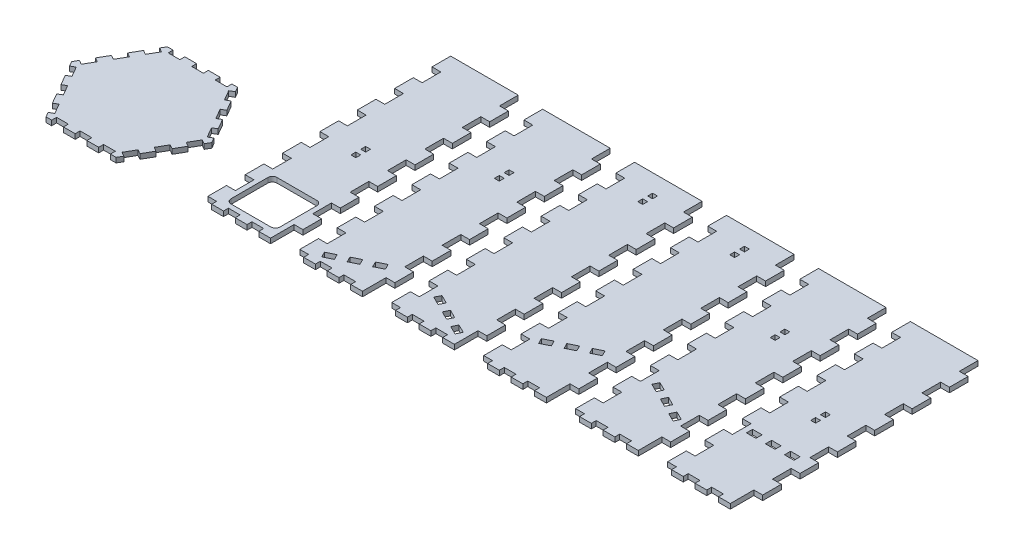
SolidWorks part; units mm, degrees
ref_plane "Front Plane" through (0, 0, 0) normal (0, 0, 1) x (1, 0, 0)
ref_plane "Top Plane" through (0, 0, 0) normal (0, 1, 0) x (1, 0, 0)
ref_plane "Right Plane" through (0, 0, 0) normal (1, 0, 0) x (0, 0, -1)
sketch "Sketch1" plane through (0, 0, 0) normal (0, 1, 0) x (1, 0, 0)
  line L0 (-22.87, -39.612) -> (-19.175, -39.612)
  line L13 (-19.175, -39.612) -> (-19.175, -36.412)
  line L14 (-19.175, -36.412) -> (-11.505, -36.412)
  line L15 (-11.505, -36.412) -> (-11.505, -39.612)
  line L16 (-11.505, -39.612) -> (-3.835, -39.612)
  line L17 (-3.835, -39.612) -> (-3.835, -36.412)
  line L18 (-3.835, -36.412) -> (3.835, -36.412)
  line L19 (3.835, -36.412) -> (3.835, -39.612)
  line L21 (-45.74, 0) -> (-43.8925, -3.2)
  line L22 (3.835, -39.612) -> (11.505, -39.612)
  line L23 (11.505, -39.612) -> (11.505, -36.412)
  line L24 (11.505, -36.412) -> (19.175, -36.412)
  line L25 (19.175, -36.412) -> (19.175, -39.612)
  line L26 (19.175, -39.612) -> (22.87, -39.612)
  line L27 (22.87, -39.612) -> (24.7175, -36.412)
  line L28 (45.74, 0) -> (22.87, 39.612) construction
  line L29 (24.7175, -36.412) -> (21.9462, -34.812)
  line L30 (21.9462, -34.812) -> (25.7812, -28.1696)
  line L31 (25.7812, -28.1696) -> (28.5525, -29.7696)
  line L32 (28.5525, -29.7696) -> (32.3875, -23.1272)
  line L33 (32.3875, -23.1272) -> (29.6162, -21.5272)
  line L34 (29.6162, -21.5272) -> (33.4512, -14.8848)
  line L35 (33.4512, -14.8848) -> (36.2225, -16.4848)
  line L36 (36.2225, -16.4848) -> (40.0575, -9.8424)
  line L37 (40.0575, -9.8424) -> (37.2862, -8.2424)
  line L38 (37.2862, -8.2424) -> (41.1212, -1.6)
  line L39 (41.1212, -1.6) -> (43.8925, -3.2)
  line L40 (43.8925, -3.2) -> (45.74, 0)
  line L41 (45.74, 0) -> (43.8925, 3.2)
  line L42 (22.87, 39.612) -> (-22.87, 39.612) construction
  line L43 (-22.87, 39.612) -> (-45.74, 0) construction
  line L44 (43.8925, 3.2) -> (41.1212, 1.6)
  line L45 (41.1212, 1.6) -> (37.2862, 8.2424)
  line L46 (37.2862, 8.2424) -> (40.0575, 9.8424)
  line L47 (40.0575, 9.8424) -> (36.2225, 16.4848)
  line L48 (36.2225, 16.4848) -> (33.4512, 14.8848)
  line L49 (33.4512, 14.8848) -> (29.6162, 21.5272)
  line L50 (29.6162, 21.5272) -> (32.3875, 23.1272)
  line L51 (32.3875, 23.1272) -> (28.5525, 29.7696)
  line L52 (28.5525, 29.7696) -> (25.7812, 28.1696)
  line L53 (25.7812, 28.1696) -> (21.9462, 34.812)
  line L54 (21.9462, 34.812) -> (24.7175, 36.412)
  line L55 (24.7175, 36.412) -> (22.87, 39.612)
  line L56 (22.87, 39.612) -> (19.175, 39.612)
  line L57 (-45.74, 0) -> (-22.87, -39.612) construction
  line L58 (-22.87, -39.612) -> (22.87, -39.612) construction
  line L59 (19.175, 39.612) -> (19.175, 36.412)
  line L60 (19.175, 36.412) -> (11.505, 36.412)
  line L61 (11.505, 36.412) -> (11.505, 39.612)
  line L62 (11.505, 39.612) -> (3.835, 39.612)
  line L63 (3.835, 39.612) -> (3.835, 36.412)
  line L64 (3.835, 36.412) -> (-3.835, 36.412)
  line L65 (-3.835, 36.412) -> (-3.835, 39.612)
  line L66 (-3.835, 39.612) -> (-11.505, 39.612)
  line L67 (-11.505, 39.612) -> (-11.505, 36.412)
  line L68 (-11.505, 36.412) -> (-19.175, 36.412)
  line L69 (-19.175, 36.412) -> (-19.175, 39.612)
  line L70 (-19.175, 39.612) -> (-22.87, 39.612)
  line L71 (-22.87, 39.612) -> (-24.7175, 36.412)
  line L72 (22.87, -39.612) -> (45.74, 0) construction
  line L73 (-43.8925, -3.2) -> (-41.1212, -1.6)
  line L74 (-24.7175, 36.412) -> (-21.9462, 34.812)
  line L75 (-21.9462, 34.812) -> (-25.7812, 28.1696)
  line L76 (-25.7812, 28.1696) -> (-28.5525, 29.7696)
  line L77 (-28.5525, 29.7696) -> (-32.3875, 23.1272)
  line L78 (-32.3875, 23.1272) -> (-29.6162, 21.5272)
  line L79 (-29.6162, 21.5272) -> (-33.4512, 14.8848)
  line L80 (-33.4512, 14.8848) -> (-36.2225, 16.4848)
  line L81 (-36.2225, 16.4848) -> (-40.0575, 9.8424)
  line L82 (-40.0575, 9.8424) -> (-37.2862, 8.2424)
  line L83 (-37.2862, 8.2424) -> (-41.1212, 1.6)
  line L84 (-41.1212, 1.6) -> (-43.8925, 3.2)
  line L85 (-43.8925, 3.2) -> (-45.74, 0)
  line L86 (-41.1212, -1.6) -> (-37.2862, -8.2424)
  line L87 (-37.2862, -8.2424) -> (-40.0575, -9.8424)
  line L88 (-40.0575, -9.8424) -> (-36.2225, -16.4848)
  line L89 (-36.2225, -16.4848) -> (-33.4512, -14.8848)
  line L90 (-33.4512, -14.8848) -> (-29.6162, -21.5272)
  line L91 (-29.6162, -21.5272) -> (-32.3875, -23.1272)
  line L92 (-32.3875, -23.1272) -> (-28.5525, -29.7696)
  line L93 (-28.5525, -29.7696) -> (-25.7812, -28.1696)
  line L94 (-25.7812, -28.1696) -> (-21.9462, -34.812)
  line L95 (-21.9462, -34.812) -> (-24.7175, -36.412)
  line L96 (-24.7175, -36.412) -> (-22.87, -39.612)
  line L97 (-21.9462, -34.812) -> (-19.175, -39.612) construction
  line L102 (19.175, -36.412) -> (24.7175, -36.412) construction
  line L103 (-19.175, -36.412) -> (-24.7175, -36.412) construction
  line L104 (80.5528, -34.8794) -> (88.2227, -34.8794)
  line L105 (88.2227, -34.8794) -> (88.2227, -31.6794)
  line L106 (88.2227, -31.6794) -> (95.8927, -31.6794)
  line L107 (95.8927, -31.6794) -> (95.8927, -34.8794)
  line L108 (95.8927, -34.8794) -> (103.5627, -34.8794)
  line L109 (103.5627, -34.8794) -> (103.5627, -31.6794)
  line L110 (103.5627, -31.6794) -> (111.2327, -31.6794)
  line L111 (111.2327, -31.6794) -> (111.2327, -34.8794)
  line L112 (111.2327, -34.8794) -> (118.9027, -34.8794)
  line L113 (80.5528, -34.8794) -> (80.5528, -31.6794)
  line L114 (80.5528, -31.6794) -> (74.8102, -31.6794)
  line L115 (74.8102, -31.6794) -> (74.8102, -19.4911)
  line L116 (74.8102, -19.4911) -> (80.5528, -19.4911)
  line L117 (80.5528, -19.4911) -> (80.5528, -7.3028)
  line L118 (80.5528, -7.3028) -> (74.8102, -7.3028)
  line L121 (118.9027, -7.3028) -> (124.6452, -7.3028)
  line L122 (124.6452, -7.3028) -> (124.6452, -19.4911)
  line L123 (124.6452, -19.4911) -> (118.9027, -19.4911)
  line L124 (118.9027, -19.4911) -> (118.9027, -34.8794)
  line L126 (21.9462, -34.812) -> (19.175, -39.612) construction
  line L250 (140.5528, -34.8794) -> (148.2227, -34.8794)
  line L265 (148.2227, -34.8794) -> (148.2227, -31.6794)
  line L266 (148.2227, -31.6794) -> (155.8927, -31.6794)
  line L267 (155.8927, -31.6794) -> (155.8927, -34.8794)
  line L268 (155.8927, -34.8794) -> (163.5627, -34.8794)
  line L269 (163.5627, -34.8794) -> (163.5627, -31.6794)
  line L270 (74.8102, -7.3028) -> (74.8102, 4.8855)
  line L271 (74.8102, 4.8855) -> (80.5528, 4.8855)
  line L272 (80.5528, 4.8855) -> (80.5528, 17.0739)
  line L273 (80.5528, 17.0739) -> (74.8102, 17.0739)
  line L274 (74.8102, 17.0739) -> (74.8102, 29.2622)
  line L275 (74.8102, 29.2622) -> (80.5528, 29.2622)
  line L276 (80.5528, 29.2622) -> (80.5528, 41.4505)
  line L277 (80.5528, 41.4505) -> (74.8102, 41.4505)
  line L278 (74.8102, 41.4505) -> (74.8102, 53.6388)
  line L279 (74.8102, 53.6388) -> (80.5528, 53.6388)
  line L280 (80.5528, 53.6388) -> (80.5528, 65.8271)
  line L281 (80.5528, 65.8271) -> (74.8102, 65.8271)
  line L282 (74.8102, 65.8271) -> (74.8102, 78.0154)
  line L283 (74.8102, 78.0154) -> (80.5528, 78.0154)
  line L284 (80.5528, 78.0154) -> (80.5528, 90.2037)
  line L285 (80.5528, 90.2037) -> (74.8102, 90.2037)
  line L286 (74.8102, 90.2037) -> (74.8102, 102.392)
  line L287 (74.8102, 102.392) -> (80.5528, 102.392)
  line L288 (80.5528, 102.392) -> (80.5528, 114.5803)
  line L289 (80.5528, 114.5803) -> (74.8102, 114.5803)
  line L290 (74.8102, 114.5803) -> (74.8102, 126.7686)
  line L291 (118.9027, -7.3028) -> (118.9027, 4.8855)
  line L292 (118.9027, 4.8855) -> (124.6452, 4.8855)
  line L293 (124.6452, 4.8855) -> (124.6452, 17.0739)
  line L294 (124.6452, 17.0739) -> (118.9027, 17.0739)
  line L295 (118.9027, 17.0739) -> (118.9027, 29.2622)
  line L296 (118.9027, 29.2622) -> (124.6452, 29.2622)
  line L297 (124.6452, 29.2622) -> (124.6452, 41.4505)
  line L298 (124.6452, 41.4505) -> (118.9027, 41.4505)
  line L299 (118.9027, 41.4505) -> (118.9027, 53.6388)
  line L300 (118.9027, 53.6388) -> (124.6452, 53.6388)
  line L301 (124.6452, 53.6388) -> (124.6452, 65.8271)
  line L302 (124.6452, 65.8271) -> (118.9027, 65.8271)
  line L303 (118.9027, 65.8271) -> (118.9027, 78.0154)
  line L304 (118.9027, 78.0154) -> (124.6452, 78.0154)
  line L305 (124.6452, 78.0154) -> (124.6452, 90.2037)
  line L306 (124.6452, 90.2037) -> (118.9027, 90.2037)
  line L307 (118.9027, 90.2037) -> (118.9027, 102.392)
  line L308 (118.9027, 102.392) -> (124.6452, 102.392)
  line L309 (124.6452, 102.392) -> (124.6452, 114.5803)
  line L310 (124.6452, 114.5803) -> (118.9027, 114.5803)
  line L311 (118.9027, 114.5803) -> (118.9027, 126.7686)
  line L312 (163.5627, -31.6794) -> (171.2327, -31.6794)
  line L313 (171.2327, -31.6794) -> (171.2327, -34.8794)
  line L314 (171.2327, -34.8794) -> (178.9027, -34.8794)
  line L315 (140.5528, -34.8794) -> (140.5528, -31.6794)
  line L316 (140.5528, -31.6794) -> (134.8102, -31.6794)
  line L317 (134.8102, -31.6794) -> (134.8102, -19.4911)
  line L318 (134.8102, -19.4911) -> (140.5528, -19.4911)
  line L319 (140.5528, -19.4911) -> (140.5528, -7.3028)
  line L320 (140.5528, -7.3028) -> (134.8102, -7.3028)
  line L322 (178.9027, -7.3028) -> (184.6452, -7.3028)
  line L323 (184.6452, -7.3028) -> (184.6452, -19.4911)
  line L324 (184.6452, -19.4911) -> (178.9027, -19.4911)
  line L325 (178.9027, -19.4911) -> (178.9027, -34.8794)
  line L326 (134.8102, -7.3028) -> (134.8102, 4.8855)
  line L327 (134.8102, 4.8855) -> (140.5528, 4.8855)
  line L328 (140.5528, 4.8855) -> (140.5528, 17.0739)
  line L329 (140.5528, 17.0739) -> (134.8102, 17.0739)
  line L330 (134.8102, 17.0739) -> (134.8102, 29.2622)
  line L331 (134.8102, 29.2622) -> (140.5528, 29.2622)
  line L332 (140.5528, 29.2622) -> (140.5528, 41.4505)
  line L333 (140.5528, 41.4505) -> (134.8102, 41.4505)
  line L334 (134.8102, 41.4505) -> (134.8102, 53.6388)
  line L335 (134.8102, 53.6388) -> (140.5528, 53.6388)
  line L336 (140.5528, 53.6388) -> (140.5528, 65.8271)
  line L337 (140.5528, 65.8271) -> (134.8102, 65.8271)
  line L338 (134.8102, 65.8271) -> (134.8102, 78.0154)
  line L339 (134.8102, 78.0154) -> (140.5528, 78.0154)
  line L340 (140.5528, 78.0154) -> (140.5528, 90.2037)
  line L341 (140.5528, 90.2037) -> (134.8102, 90.2037)
  line L342 (134.8102, 90.2037) -> (134.8102, 102.392)
  line L343 (134.8102, 102.392) -> (140.5528, 102.392)
  line L344 (140.5528, 102.392) -> (140.5528, 114.5803)
  line L345 (140.5528, 114.5803) -> (134.8102, 114.5803)
  line L346 (134.8102, 114.5803) -> (134.8102, 126.7686)
  line L347 (178.9027, -7.3028) -> (178.9027, 4.8855)
  line L348 (178.9027, 4.8855) -> (184.6452, 4.8855)
  line L349 (184.6452, 4.8855) -> (184.6452, 17.0739)
  line L350 (184.6452, 17.0739) -> (178.9027, 17.0739)
  line L351 (178.9027, 17.0739) -> (178.9027, 29.2622)
  line L352 (178.9027, 29.2622) -> (184.6452, 29.2622)
  line L353 (184.6452, 29.2622) -> (184.6452, 41.4505)
  line L354 (184.6452, 41.4505) -> (178.9027, 41.4505)
  line L355 (178.9027, 41.4505) -> (178.9027, 53.6388)
  line L356 (178.9027, 53.6388) -> (184.6452, 53.6388)
  line L357 (184.6452, 53.6388) -> (184.6452, 65.8271)
  line L358 (184.6452, 65.8271) -> (178.9027, 65.8271)
  line L359 (178.9027, 65.8271) -> (178.9027, 78.0154)
  line L360 (178.9027, 78.0154) -> (184.6452, 78.0154)
  line L361 (184.6452, 78.0154) -> (184.6452, 90.2037)
  line L362 (184.6452, 90.2037) -> (178.9027, 90.2037)
  line L363 (178.9027, 90.2037) -> (178.9027, 102.392)
  line L364 (178.9027, 102.392) -> (184.6452, 102.392)
  line L365 (184.6452, 102.392) -> (184.6452, 114.5803)
  line L366 (184.6452, 114.5803) -> (178.9027, 114.5803)
  line L367 (178.9027, 114.5803) -> (178.9027, 126.7686)
  line L369 (200.5528, -34.8794) -> (208.2227, -34.8794)
  line L370 (208.2227, -34.8794) -> (208.2227, -31.6794)
  line L371 (208.2227, -31.6794) -> (215.8927, -31.6794)
  line L372 (215.8927, -31.6794) -> (215.8927, -34.8794)
  line L373 (215.8927, -34.8794) -> (223.5627, -34.8794)
  line L374 (223.5627, -34.8794) -> (223.5627, -31.6794)
  line L375 (223.5627, -31.6794) -> (231.2327, -31.6794)
  line L376 (231.2327, -31.6794) -> (231.2327, -34.8794)
  line L377 (231.2327, -34.8794) -> (238.9027, -34.8794)
  line L378 (200.5528, -34.8794) -> (200.5528, -31.6794)
  line L379 (200.5528, -31.6794) -> (194.8102, -31.6794)
  line L380 (194.8102, -31.6794) -> (194.8102, -19.4911)
  line L381 (194.8102, -19.4911) -> (200.5528, -19.4911)
  line L382 (200.5528, -19.4911) -> (200.5528, -7.3028)
  line L383 (200.5528, -7.3028) -> (194.8102, -7.3028)
  line L385 (238.9027, -7.3028) -> (244.6452, -7.3028)
  line L386 (244.6452, -7.3028) -> (244.6452, -19.4911)
  line L387 (244.6452, -19.4911) -> (238.9027, -19.4911)
  line L388 (238.9027, -19.4911) -> (238.9027, -34.8794)
  line L389 (194.8102, -7.3028) -> (194.8102, 4.8855)
  line L390 (194.8102, 4.8855) -> (200.5528, 4.8855)
  line L391 (200.5528, 4.8855) -> (200.5528, 17.0739)
  line L392 (200.5528, 17.0739) -> (194.8102, 17.0739)
  line L393 (194.8102, 17.0739) -> (194.8102, 29.2622)
  line L394 (194.8102, 29.2622) -> (200.5528, 29.2622)
  line L395 (200.5528, 29.2622) -> (200.5528, 41.4505)
  line L396 (200.5528, 41.4505) -> (194.8102, 41.4505)
  line L397 (194.8102, 41.4505) -> (194.8102, 53.6388)
  line L398 (194.8102, 53.6388) -> (200.5528, 53.6388)
  line L399 (200.5528, 53.6388) -> (200.5528, 65.8271)
  line L400 (200.5528, 65.8271) -> (194.8102, 65.8271)
  line L401 (194.8102, 65.8271) -> (194.8102, 78.0154)
  line L402 (194.8102, 78.0154) -> (200.5528, 78.0154)
  line L403 (200.5528, 78.0154) -> (200.5528, 90.2037)
  line L404 (200.5528, 90.2037) -> (194.8102, 90.2037)
  line L405 (194.8102, 90.2037) -> (194.8102, 102.392)
  line L406 (194.8102, 102.392) -> (200.5528, 102.392)
  line L407 (200.5528, 102.392) -> (200.5528, 114.5803)
  line L408 (200.5528, 114.5803) -> (194.8102, 114.5803)
  line L409 (194.8102, 114.5803) -> (194.8102, 126.7686)
  line L410 (238.9027, -7.3028) -> (238.9027, 4.8855)
  line L411 (238.9027, 4.8855) -> (244.6452, 4.8855)
  line L412 (244.6452, 4.8855) -> (244.6452, 17.0739)
  line L413 (244.6452, 17.0739) -> (238.9027, 17.0739)
  line L414 (238.9027, 17.0739) -> (238.9027, 29.2622)
  line L415 (238.9027, 29.2622) -> (244.6452, 29.2622)
  line L416 (244.6452, 29.2622) -> (244.6452, 41.4505)
  line L417 (244.6452, 41.4505) -> (238.9027, 41.4505)
  line L418 (238.9027, 41.4505) -> (238.9027, 53.6388)
  line L419 (238.9027, 53.6388) -> (244.6452, 53.6388)
  line L420 (244.6452, 53.6388) -> (244.6452, 65.8271)
  line L421 (244.6452, 65.8271) -> (238.9027, 65.8271)
  line L422 (238.9027, 65.8271) -> (238.9027, 78.0154)
  line L423 (238.9027, 78.0154) -> (244.6452, 78.0154)
  line L424 (244.6452, 78.0154) -> (244.6452, 90.2037)
  line L425 (244.6452, 90.2037) -> (238.9027, 90.2037)
  line L426 (238.9027, 90.2037) -> (238.9027, 102.392)
  line L427 (238.9027, 102.392) -> (244.6452, 102.392)
  line L428 (244.6452, 102.392) -> (244.6452, 114.5803)
  line L429 (244.6452, 114.5803) -> (238.9027, 114.5803)
  line L430 (238.9027, 114.5803) -> (238.9027, 126.7686)
  line L432 (260.5528, -34.8794) -> (268.2227, -34.8794)
  line L433 (268.2227, -34.8794) -> (268.2227, -31.6794)
  line L434 (268.2227, -31.6794) -> (275.8927, -31.6794)
  line L435 (275.8927, -31.6794) -> (275.8927, -34.8794)
  line L436 (275.8927, -34.8794) -> (283.5627, -34.8794)
  line L437 (283.5627, -34.8794) -> (283.5627, -31.6794)
  line L438 (283.5627, -31.6794) -> (291.2327, -31.6794)
  line L439 (291.2327, -31.6794) -> (291.2327, -34.8794)
  line L440 (291.2327, -34.8794) -> (298.9027, -34.8794)
  line L441 (260.5528, -34.8794) -> (260.5528, -31.6794)
  line L442 (260.5528, -31.6794) -> (254.8102, -31.6794)
  line L443 (254.8102, -31.6794) -> (254.8102, -19.4911)
  line L444 (254.8102, -19.4911) -> (260.5528, -19.4911)
  line L445 (260.5528, -19.4911) -> (260.5528, -7.3028)
  line L446 (260.5528, -7.3028) -> (254.8102, -7.3028)
  line L448 (298.9027, -7.3028) -> (304.6452, -7.3028)
  line L449 (304.6452, -7.3028) -> (304.6452, -19.4911)
  line L450 (304.6452, -19.4911) -> (298.9027, -19.4911)
  line L451 (298.9027, -19.4911) -> (298.9027, -34.8794)
  line L452 (254.8102, -7.3028) -> (254.8102, 4.8855)
  line L453 (254.8102, 4.8855) -> (260.5528, 4.8855)
  line L454 (260.5528, 4.8855) -> (260.5528, 17.0739)
  line L455 (260.5528, 17.0739) -> (254.8102, 17.0739)
  line L456 (254.8102, 17.0739) -> (254.8102, 29.2622)
  line L457 (254.8102, 29.2622) -> (260.5528, 29.2622)
  line L458 (260.5528, 29.2622) -> (260.5528, 41.4505)
  line L459 (260.5528, 41.4505) -> (254.8102, 41.4505)
  line L460 (254.8102, 41.4505) -> (254.8102, 53.6388)
  line L461 (254.8102, 53.6388) -> (260.5528, 53.6388)
  line L462 (260.5528, 53.6388) -> (260.5528, 65.8271)
  line L463 (260.5528, 65.8271) -> (254.8102, 65.8271)
  line L464 (254.8102, 65.8271) -> (254.8102, 78.0154)
  line L465 (254.8102, 78.0154) -> (260.5528, 78.0154)
  line L466 (260.5528, 78.0154) -> (260.5528, 90.2037)
  line L467 (260.5528, 90.2037) -> (254.8102, 90.2037)
  line L468 (254.8102, 90.2037) -> (254.8102, 102.392)
  line L469 (254.8102, 102.392) -> (260.5528, 102.392)
  line L470 (260.5528, 102.392) -> (260.5528, 114.5803)
  line L471 (260.5528, 114.5803) -> (254.8102, 114.5803)
  line L472 (254.8102, 114.5803) -> (254.8102, 126.7686)
  line L473 (298.9027, -7.3028) -> (298.9027, 4.8855)
  line L474 (298.9027, 4.8855) -> (304.6452, 4.8855)
  line L475 (304.6452, 4.8855) -> (304.6452, 17.0739)
  line L476 (304.6452, 17.0739) -> (298.9027, 17.0739)
  line L477 (298.9027, 17.0739) -> (298.9027, 29.2622)
  line L478 (298.9027, 29.2622) -> (304.6452, 29.2622)
  line L479 (304.6452, 29.2622) -> (304.6452, 41.4505)
  line L480 (304.6452, 41.4505) -> (298.9027, 41.4505)
  line L481 (298.9027, 41.4505) -> (298.9027, 53.6388)
  line L482 (298.9027, 53.6388) -> (304.6452, 53.6388)
  line L483 (304.6452, 53.6388) -> (304.6452, 65.8271)
  line L484 (304.6452, 65.8271) -> (298.9027, 65.8271)
  line L485 (298.9027, 65.8271) -> (298.9027, 78.0154)
  line L486 (298.9027, 78.0154) -> (304.6452, 78.0154)
  line L487 (304.6452, 78.0154) -> (304.6452, 90.2037)
  line L488 (304.6452, 90.2037) -> (298.9027, 90.2037)
  line L489 (298.9027, 90.2037) -> (298.9027, 102.392)
  line L490 (298.9027, 102.392) -> (304.6452, 102.392)
  line L491 (304.6452, 102.392) -> (304.6452, 114.5803)
  line L492 (304.6452, 114.5803) -> (298.9027, 114.5803)
  line L493 (298.9027, 114.5803) -> (298.9027, 126.7686)
  line L495 (320.5528, -34.8794) -> (328.2227, -34.8794)
  line L496 (328.2227, -34.8794) -> (328.2227, -31.6794)
  line L497 (328.2227, -31.6794) -> (335.8927, -31.6794)
  line L498 (335.8927, -31.6794) -> (335.8927, -34.8794)
  line L499 (335.8927, -34.8794) -> (343.5627, -34.8794)
  line L500 (343.5627, -34.8794) -> (343.5627, -31.6794)
  line L501 (343.5627, -31.6794) -> (351.2327, -31.6794)
  line L502 (351.2327, -31.6794) -> (351.2327, -34.8794)
  line L503 (351.2327, -34.8794) -> (358.9027, -34.8794)
  line L504 (320.5528, -34.8794) -> (320.5528, -31.6794)
  line L505 (320.5528, -31.6794) -> (314.8102, -31.6794)
  line L506 (314.8102, -31.6794) -> (314.8102, -19.4911)
  line L507 (314.8102, -19.4911) -> (320.5528, -19.4911)
  line L508 (320.5528, -19.4911) -> (320.5528, -7.3028)
  line L509 (320.5528, -7.3028) -> (314.8102, -7.3028)
  line L511 (358.9027, -7.3028) -> (364.6452, -7.3028)
  line L512 (364.6452, -7.3028) -> (364.6452, -19.4911)
  line L513 (364.6452, -19.4911) -> (358.9027, -19.4911)
  line L514 (358.9027, -19.4911) -> (358.9027, -34.8794)
  line L515 (314.8102, -7.3028) -> (314.8102, 4.8855)
  line L516 (314.8102, 4.8855) -> (320.5528, 4.8855)
  line L517 (320.5528, 4.8855) -> (320.5528, 17.0739)
  line L518 (320.5528, 17.0739) -> (314.8102, 17.0739)
  line L519 (314.8102, 17.0739) -> (314.8102, 29.2622)
  line L520 (314.8102, 29.2622) -> (320.5528, 29.2622)
  line L521 (320.5528, 29.2622) -> (320.5528, 41.4505)
  line L522 (320.5528, 41.4505) -> (314.8102, 41.4505)
  line L523 (314.8102, 41.4505) -> (314.8102, 53.6388)
  line L524 (314.8102, 53.6388) -> (320.5528, 53.6388)
  line L525 (320.5528, 53.6388) -> (320.5528, 65.8271)
  line L526 (320.5528, 65.8271) -> (314.8102, 65.8271)
  line L527 (314.8102, 65.8271) -> (314.8102, 78.0154)
  line L528 (314.8102, 78.0154) -> (320.5528, 78.0154)
  line L529 (320.5528, 78.0154) -> (320.5528, 90.2037)
  line L530 (320.5528, 90.2037) -> (314.8102, 90.2037)
  line L531 (314.8102, 90.2037) -> (314.8102, 102.392)
  line L532 (314.8102, 102.392) -> (320.5528, 102.392)
  line L533 (320.5528, 102.392) -> (320.5528, 114.5803)
  line L534 (320.5528, 114.5803) -> (314.8102, 114.5803)
  line L535 (314.8102, 114.5803) -> (314.8102, 126.7686)
  line L536 (358.9027, -7.3028) -> (358.9027, 4.8855)
  line L537 (358.9027, 4.8855) -> (364.6452, 4.8855)
  line L538 (364.6452, 4.8855) -> (364.6452, 17.0739)
  line L539 (364.6452, 17.0739) -> (358.9027, 17.0739)
  line L540 (358.9027, 17.0739) -> (358.9027, 29.2622)
  line L541 (358.9027, 29.2622) -> (364.6452, 29.2622)
  line L542 (364.6452, 29.2622) -> (364.6452, 41.4505)
  line L543 (364.6452, 41.4505) -> (358.9027, 41.4505)
  line L544 (358.9027, 41.4505) -> (358.9027, 53.6388)
  line L545 (358.9027, 53.6388) -> (364.6452, 53.6388)
  line L546 (364.6452, 53.6388) -> (364.6452, 65.8271)
  line L547 (364.6452, 65.8271) -> (358.9027, 65.8271)
  line L548 (358.9027, 65.8271) -> (358.9027, 78.0154)
  line L549 (358.9027, 78.0154) -> (364.6452, 78.0154)
  line L550 (364.6452, 78.0154) -> (364.6452, 90.2037)
  line L551 (364.6452, 90.2037) -> (358.9027, 90.2037)
  line L552 (358.9027, 90.2037) -> (358.9027, 102.392)
  line L553 (358.9027, 102.392) -> (364.6452, 102.392)
  line L554 (364.6452, 102.392) -> (364.6452, 114.5803)
  line L555 (364.6452, 114.5803) -> (358.9027, 114.5803)
  line L556 (358.9027, 114.5803) -> (358.9027, 126.7686)
  line L558 (380.5528, -34.8794) -> (388.2227, -34.8794)
  line L559 (388.2227, -34.8794) -> (388.2227, -31.6794)
  line L560 (388.2227, -31.6794) -> (395.8927, -31.6794)
  line L561 (395.8927, -31.6794) -> (395.8927, -34.8794)
  line L562 (395.8927, -34.8794) -> (403.5627, -34.8794)
  line L563 (403.5627, -34.8794) -> (403.5627, -31.6794)
  line L564 (403.5627, -31.6794) -> (411.2327, -31.6794)
  line L565 (411.2327, -31.6794) -> (411.2327, -34.8794)
  line L566 (411.2327, -34.8794) -> (418.9027, -34.8794)
  line L567 (380.5528, -34.8794) -> (380.5528, -31.6794)
  line L568 (380.5528, -31.6794) -> (374.8102, -31.6794)
  line L569 (374.8102, -31.6794) -> (374.8102, -19.4911)
  line L570 (374.8102, -19.4911) -> (380.5528, -19.4911)
  line L571 (380.5528, -19.4911) -> (380.5528, -7.3028)
  line L572 (380.5528, -7.3028) -> (374.8102, -7.3028)
  line L574 (418.9027, -7.3028) -> (424.6452, -7.3028)
  line L575 (424.6452, -7.3028) -> (424.6452, -19.4911)
  line L576 (424.6452, -19.4911) -> (418.9027, -19.4911)
  line L577 (418.9027, -19.4911) -> (418.9027, -34.8794)
  line L578 (374.8102, -7.3028) -> (374.8102, 4.8855)
  line L579 (374.8102, 4.8855) -> (380.5528, 4.8855)
  line L580 (380.5528, 4.8855) -> (380.5528, 17.0739)
  line L581 (380.5528, 17.0739) -> (374.8102, 17.0739)
  line L582 (374.8102, 17.0739) -> (374.8102, 29.2622)
  line L583 (374.8102, 29.2622) -> (380.5528, 29.2622)
  line L584 (380.5528, 29.2622) -> (380.5528, 41.4505)
  line L585 (380.5528, 41.4505) -> (374.8102, 41.4505)
  line L586 (374.8102, 41.4505) -> (374.8102, 53.6388)
  line L587 (374.8102, 53.6388) -> (380.5528, 53.6388)
  line L588 (380.5528, 53.6388) -> (380.5528, 65.8271)
  line L589 (380.5528, 65.8271) -> (374.8102, 65.8271)
  line L590 (374.8102, 65.8271) -> (374.8102, 78.0154)
  line L591 (374.8102, 78.0154) -> (380.5528, 78.0154)
  line L592 (380.5528, 78.0154) -> (380.5528, 90.2037)
  line L593 (380.5528, 90.2037) -> (374.8102, 90.2037)
  line L594 (374.8102, 90.2037) -> (374.8102, 102.392)
  line L595 (374.8102, 102.392) -> (380.5528, 102.392)
  line L596 (380.5528, 102.392) -> (380.5528, 114.5803)
  line L597 (380.5528, 114.5803) -> (374.8102, 114.5803)
  line L598 (374.8102, 114.5803) -> (374.8102, 126.7686)
  line L599 (418.9027, -7.3028) -> (418.9027, 4.8855)
  line L600 (418.9027, 4.8855) -> (424.6452, 4.8855)
  line L601 (424.6452, 4.8855) -> (424.6452, 17.0739)
  line L602 (424.6452, 17.0739) -> (418.9027, 17.0739)
  line L603 (418.9027, 17.0739) -> (418.9027, 29.2622)
  line L604 (418.9027, 29.2622) -> (424.6452, 29.2622)
  line L605 (424.6452, 29.2622) -> (424.6452, 41.4505)
  line L606 (424.6452, 41.4505) -> (418.9027, 41.4505)
  line L607 (418.9027, 41.4505) -> (418.9027, 53.6388)
  line L608 (418.9027, 53.6388) -> (424.6452, 53.6388)
  line L609 (424.6452, 53.6388) -> (424.6452, 65.8271)
  line L610 (424.6452, 65.8271) -> (418.9027, 65.8271)
  line L611 (418.9027, 65.8271) -> (418.9027, 78.0154)
  line L612 (418.9027, 78.0154) -> (424.6452, 78.0154)
  line L613 (424.6452, 78.0154) -> (424.6452, 90.2037)
  line L614 (424.6452, 90.2037) -> (418.9027, 90.2037)
  line L615 (418.9027, 90.2037) -> (418.9027, 102.392)
  line L616 (418.9027, 102.392) -> (424.6452, 102.392)
  line L617 (424.6452, 102.392) -> (424.6452, 114.5803)
  line L618 (424.6452, 114.5803) -> (418.9027, 114.5803)
  line L619 (418.9027, 114.5803) -> (418.9027, 126.7686)
  line L621 (144.4326, -25.24) -> (149.9783, -22.4678)
  line L622 (144.4326, -25.24) -> (146.2212, -28.8179)
  line L623 (146.2212, -28.8179) -> (151.7669, -26.0457)
  line L624 (149.9783, -22.4678) -> (151.7669, -26.0457)
  line L625 (155.524, -19.6956) -> (161.0697, -16.9234)
  line L626 (155.524, -19.6956) -> (157.3126, -23.2735)
  line L627 (157.3126, -23.2735) -> (162.8583, -20.5012)
  line L628 (161.0697, -16.9234) -> (162.8583, -20.5012)
  line L632 (166.6154, -14.1512) -> (172.1611, -11.3789)
  line L633 (166.6154, -14.1512) -> (168.404, -17.729)
  line L634 (168.404, -17.729) -> (173.9497, -14.9568)
  line L635 (172.1611, -11.3789) -> (173.9497, -14.9568)
  line L636 (118.9027, 126.7686) -> (74.8102, 126.7686)
  line L637 (134.8102, 126.7686) -> (178.9027, 126.7686)
  line L638 (194.8102, 126.7686) -> (238.9027, 126.7686)
  line L639 (254.8102, 126.7686) -> (298.9027, 126.7686)
  line L640 (314.8102, 126.7686) -> (358.9027, 126.7686)
  line L641 (374.8102, 126.7686) -> (418.9027, 126.7686)
  line L642 (-41.1212, -1.6) -> (-42.045, 0) construction
  line L643 (-42.045, 0) -> (-41.1212, 1.6) construction
  line L644 (41.1212, -1.6) -> (42.045, 0) construction
  line L645 (42.045, 0) -> (41.1212, 1.6) construction
  line L646 (-21.0225, -36.412) -> (-22.87, -39.612) construction
  line L647 (21.0225, -36.412) -> (22.87, -39.612) construction
  line L648 (138.7077, -31.6794) -> (145.8635, -28.1023) construction
  line L649 (173.592, -14.2412) -> (180.7477, -10.6642) construction
  line L650 (189.7277, 136.633) -> (189.7277, -43.0289) construction
  line L651 (138.7077, -34.8794) -> (180.7477, -34.8794) construction
  line L652 (207.2943, -11.3789) -> (205.5058, -14.9568)
  line L653 (211.0515, -17.729) -> (205.5058, -14.9568)
  line L654 (212.84, -14.1512) -> (211.0515, -17.729)
  line L655 (212.84, -14.1512) -> (207.2943, -11.3789)
  line L656 (218.3857, -16.9234) -> (216.5972, -20.5012)
  line L657 (222.1429, -23.2735) -> (216.5972, -20.5012)
  line L658 (223.9314, -19.6956) -> (222.1429, -23.2735)
  line L659 (223.9314, -19.6956) -> (218.3857, -16.9234)
  line L660 (229.4771, -22.4678) -> (227.6886, -26.0457)
  line L661 (233.2343, -28.8179) -> (227.6886, -26.0457)
  line L662 (235.0228, -25.24) -> (233.2343, -28.8179)
  line L663 (235.0228, -25.24) -> (229.4771, -22.4678)
  line L664 (252.6938, -10.4795) -> (309.7277, -10.4795) construction
  line L665 (258.7077, -34.8794) -> (300.7477, -34.8794) construction
  line L666 (258.7077, -10.4795) -> (265.8635, -6.9025) construction
  line L667 (265.8635, -6.9025) -> (264.0749, -3.3246)
  line L668 (264.0749, -3.3246) -> (269.6206, -0.5524)
  line L669 (269.6206, -0.5524) -> (271.4092, -4.1302)
  line L670 (271.4092, -4.1302) -> (265.8635, -6.9025)
  line L671 (275.1663, 2.2199) -> (276.9549, -1.358)
  line L672 (276.9549, -1.358) -> (282.5006, 1.4142)
  line L673 (282.5006, 1.4142) -> (280.712, 4.9921)
  line L674 (280.712, 4.9921) -> (275.1663, 2.2199)
  line L675 (286.2577, 7.7643) -> (288.0463, 4.1864)
  line L676 (288.0463, 4.1864) -> (293.592, 6.9586)
  line L677 (293.592, 6.9586) -> (291.8034, 10.5365)
  line L678 (291.8034, 10.5365) -> (286.2577, 7.7643)
  line L679 (293.592, 6.9586) -> (300.7477, 10.5357) construction
  line L680 (309.7277, 136.633) -> (309.7277, -43.0289) construction
  line L681 (327.652, 10.5365) -> (333.1977, 7.7643)
  line L682 (325.8635, 6.9586) -> (327.652, 10.5365)
  line L683 (331.4092, 4.1864) -> (325.8635, 6.9586)
  line L684 (333.1977, 7.7643) -> (331.4092, 4.1864)
  line L685 (338.7434, 4.9921) -> (344.2891, 2.2199)
  line L686 (336.9549, 1.4142) -> (338.7434, 4.9921)
  line L687 (342.5006, -1.358) -> (336.9549, 1.4142)
  line L688 (344.2891, 2.2199) -> (342.5006, -1.358)
  line L689 (348.0463, -4.1302) -> (353.592, -6.9025)
  line L690 (349.8348, -0.5524) -> (348.0463, -4.1302)
  line L691 (355.3805, -3.3246) -> (349.8348, -0.5524)
  line L692 (353.592, -6.9025) -> (355.3805, -3.3246)
  line L693 (384.2277, 14.3606) -> (384.2277, 10.3606)
  line L694 (384.2277, 10.3606) -> (390.4277, 10.3606)
  line L695 (390.4277, 10.3606) -> (390.4277, 14.3606)
  line L696 (390.4277, 14.3606) -> (384.2277, 14.3606)
  line L697 (396.6277, 14.3606) -> (396.6277, 10.3606)
  line L698 (396.6277, 10.3606) -> (402.8277, 10.3606)
  line L699 (402.8277, 10.3606) -> (402.8277, 14.3606)
  line L700 (402.8277, 14.3606) -> (396.6277, 14.3606)
  line L701 (409.0277, 14.3606) -> (409.0277, 10.3606)
  line L702 (409.0277, 10.3606) -> (415.2277, 10.3606)
  line L703 (415.2277, 10.3606) -> (415.2277, 14.3606)
  line L704 (415.2277, 14.3606) -> (409.0277, 14.3606)
  line L705 (384.2277, 10.3606) -> (380.5528, 10.3606) construction
  line L706 (415.2277, 10.3606) -> (418.9027, 10.3606) construction
  line L707 (86.7528, 1.5206) -> (112.7027, 1.5206)
  line L708 (112.7027, -28.4794) -> (86.7528, -28.4794)
  line L709 (83.7528, -1.4794) -> (83.7528, -25.4794)
  line L710 (115.7027, -1.4794) -> (115.7027, -25.4794)
  line L711 (249.7277, 136.633) -> (249.7277, -43.0289) construction
  line L712 (398.1277, 47.9606) -> (401.3277, 47.9606)
  line L713 (398.1277, 47.9606) -> (398.1277, 44.7606)
  line L714 (398.1277, 44.7606) -> (401.3277, 44.7606)
  line L715 (401.3277, 47.9606) -> (401.3277, 44.7606)
  line L716 (398.1277, 41.5606) -> (401.3277, 41.5606)
  line L717 (398.1277, 41.5606) -> (398.1277, 38.3606)
  line L718 (398.1277, 38.3606) -> (401.3277, 38.3606)
  line L719 (401.3277, 41.5606) -> (401.3277, 38.3606)
  line L720 (98.1277, 41.5606) -> (98.1277, 38.3606)
  line L721 (101.3277, 38.3606) -> (98.1277, 38.3606)
  line L722 (101.3277, 41.5606) -> (101.3277, 38.3606)
  line L723 (101.3277, 41.5606) -> (98.1277, 41.5606)
  line L724 (98.1277, 47.9606) -> (98.1277, 44.7606)
  line L725 (101.3277, 44.7606) -> (98.1277, 44.7606)
  line L726 (101.3277, 47.9606) -> (101.3277, 44.7606)
  line L727 (101.3277, 47.9606) -> (98.1277, 47.9606)
  line L728 (158.1277, 75.1606) -> (158.1277, 71.9606)
  line L729 (161.3277, 71.9606) -> (158.1277, 71.9606)
  line L730 (161.3277, 75.1606) -> (161.3277, 71.9606)
  line L731 (161.3277, 75.1606) -> (158.1277, 75.1606)
  line L732 (158.1277, 81.5606) -> (158.1277, 78.3606)
  line L733 (161.3277, 78.3606) -> (158.1277, 78.3606)
  line L734 (161.3277, 81.5606) -> (161.3277, 78.3606)
  line L735 (161.3277, 81.5606) -> (158.1277, 81.5606)
  line L736 (338.1277, 81.5606) -> (341.3277, 81.5606)
  line L737 (338.1277, 81.5606) -> (338.1277, 78.3606)
  line L738 (338.1277, 78.3606) -> (341.3277, 78.3606)
  line L739 (341.3277, 81.5606) -> (341.3277, 78.3606)
  line L740 (338.1277, 75.1606) -> (341.3277, 75.1606)
  line L741 (338.1277, 75.1606) -> (338.1277, 71.9606)
  line L742 (338.1277, 71.9606) -> (341.3277, 71.9606)
  line L743 (341.3277, 75.1606) -> (341.3277, 71.9606)
  line L744 (218.1277, 108.7606) -> (218.1277, 105.5606)
  line L745 (221.3277, 105.5606) -> (218.1277, 105.5606)
  line L746 (221.3277, 108.7606) -> (221.3277, 105.5606)
  line L747 (221.3277, 108.7606) -> (218.1277, 108.7606)
  line L748 (218.1277, 115.1606) -> (218.1277, 111.9606)
  line L749 (221.3277, 111.9606) -> (218.1277, 111.9606)
  line L750 (221.3277, 115.1606) -> (221.3277, 111.9606)
  line L751 (221.3277, 115.1606) -> (218.1277, 115.1606)
  line L752 (278.1277, 115.1606) -> (281.3277, 115.1606)
  line L753 (278.1277, 115.1606) -> (278.1277, 111.9606)
  line L754 (278.1277, 111.9606) -> (281.3277, 111.9606)
  line L755 (281.3277, 115.1606) -> (281.3277, 111.9606)
  line L756 (278.1277, 108.7606) -> (281.3277, 108.7606)
  line L757 (278.1277, 108.7606) -> (278.1277, 105.5606)
  line L758 (278.1277, 105.5606) -> (281.3277, 105.5606)
  line L759 (281.3277, 108.7606) -> (281.3277, 105.5606)
  circle A0 centre (0, 0) radius 39.612 construction
  arc A5 (86.7528, -28.4794) -> (83.7528, -25.4794) centre (86.7528, -25.4794) cw
  arc A6 (83.7528, -1.4794) -> (86.7528, 1.5206) centre (86.7528, -1.4794) cw
  arc A7 (112.7027, 1.5206) -> (115.7027, -1.4794) centre (112.7027, -1.4794) cw
  arc A8 (115.7027, -25.4794) -> (112.7027, -28.4794) centre (112.7027, -25.4794) cw
  point P498 (304.6452, -13.3969)
  point P582 (158.1277, 79.9606)
  dimension "D9" = 79.224
  dimension "D66" = 38.3499
  dimension "D79" = 3.2
  dimension "D10" = 38.3499
  dimension "D83" = 5.7426
  dimension "D45" = 5.7426
  dimension "D12" = 120
  dimension "D2" = 3.695
  dimension "D3" = 7.67
  dimension "D5" = 38.3499
  dimension "D11" = 12.1883
  dimension "D13" = 3.2
  dimension "D14" = 5.5426
  dimension "D86" = 15.3883
  dimension "D17" = 6.2
  dimension "D18" = 6.2
  dimension "D22" = 158.448
  dimension "D23" = 72.824
  dimension "D24" = 84.0899
  dimension "D25" = 42.045
  dimension "D19" = 6.2
  dimension "D20" = 10.165
  dimension "D26" = 5.0825
  dimension "D21" = 42.04
  dimension "D27" = 38.3499
  dimension "D28" = 1.845
  dimension "D32" = 21.1999
  dimension "D33" = 42.04
  dimension "D34" = 1.845
  dimension "D35" = 38.3499
  dimension "D36" = 4
  dimension "D37" = 6.2
  dimension "D38" = 6.2
  dimension "D39" = 6.2
  dimension "D40" = 8
  dimension "D41" = 26.56
  dimension "D42" = 10.165
  dimension "D43" = 5.0825
  dimension "D44" = 42.04
  dimension "D46" = 6.2
  dimension "D47" = 6.2
  dimension "D48" = 6.2
  dimension "D29" = 8
  dimension "D30" = 21.0152
  dimension "D16" = 3.2
  dimension "D31" = 4
  dimension "D49" = 4
  dimension "D50" = 3.2
  dimension "D51" = 3.2
  dimension "D52" = 3.2
  dimension "D53" = 30
  dimension "D54" = 3
  dimension "D55" = 3
  dimension "D56" = 3
  dimension "D57" = 3
  dimension "D58" = 3
  dimension "D59" = 3
  dimension "D60" = 3
  dimension "D61" = 3
  dimension "D62" = 3.2
  dimension "D63" = 3.2
  dimension "D64" = 3.2
  dimension "D65" = 17.575
  dimension "D67" = 5.0825
  dimension "D68" = 3.2
  dimension "D69" = 3.2
  dimension "D70" = 17.575
  dimension "D71" = 24
  dimension "D72" = 24
  dimension "D73" = 3.2
  dimension "D74" = 3.2
  dimension "D75" = 17.575
  dimension "D76" = 24
  dimension "D77" = 3.2
  dimension "D78" = 3.2
  dimension "D15" = 6
extrude "Boss-Extrude3" add sketch "Sketch1" along normal blind 3.2
equation "\"Thick\"=3.2"
equation "\"angletabwidth\"=4"
equation "\"D26@Sketch1\"=\"D20@Sketch1\"/2"
equation "\"D28@Sketch1\"=(\"D21@Sketch1\"-\"D27@Sketch1\")/2"
equation "\"D34@Sketch1\"=(\"D33@Sketch1\"-\"D35@Sketch1\")/2"
equation "\"D43@Sketch1\"=\"D42@Sketch1\"/2"
equation "\"D65@Sketch1\"=(\"D66@Sketch1\"/2)-(\"D62@Sketch1\"/2)"
equation "\"D67@Sketch1\"=\"D26@Sketch1\""
equation "\"D75@Sketch1\"=\"D65@Sketch1\""
